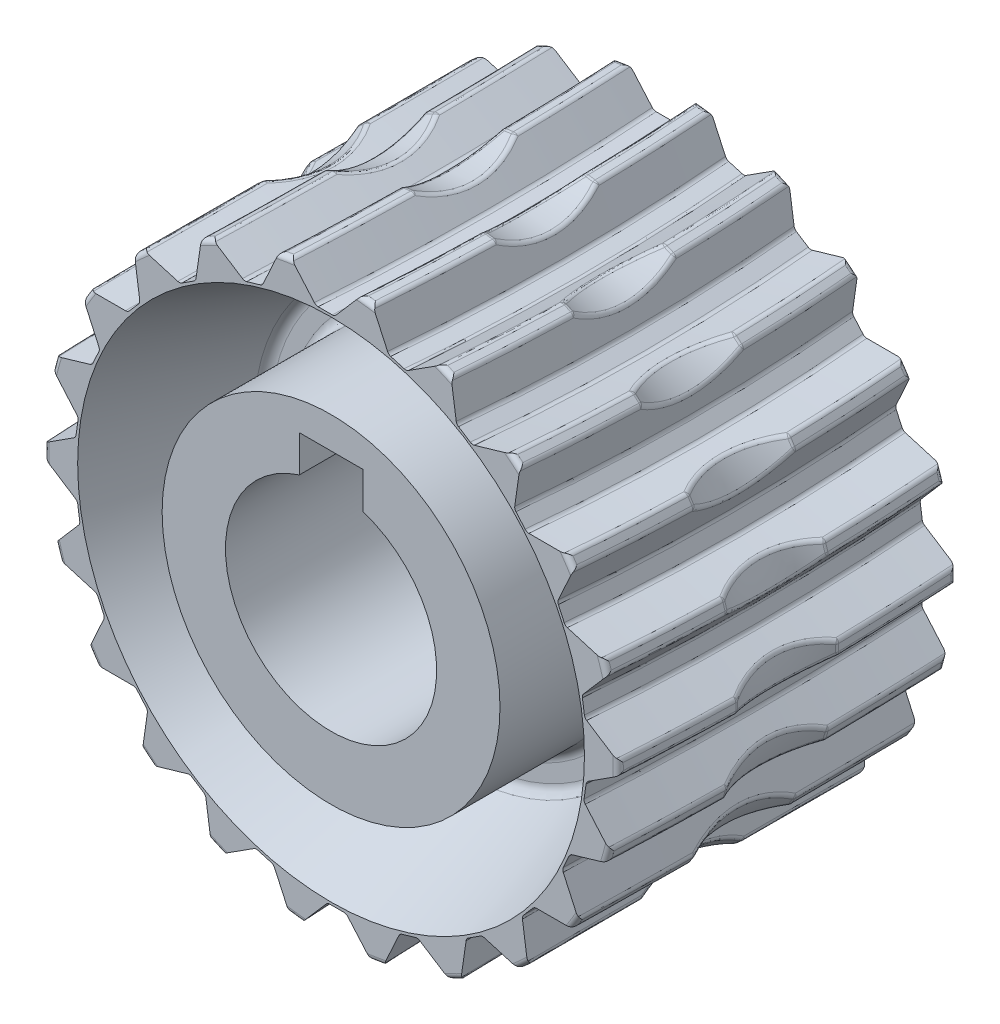
SolidWorks part; units mm, degrees
material "AISI 1020"
ref_plane "Front Plane" through (0, 0, 0) normal (0, 0, 1) x (1, 0, 0)
ref_plane "Top Plane" through (0, 0, 0) normal (0, 1, 0) x (1, 0, 0)
ref_plane "Right Plane" through (0, 0, 0) normal (1, 0, 0) x (0, 0, -1)
sketch "Sketch2" plane through (0, 0, 0) normal (0, 0, 1) x (1, 0, 0)
  circle A0 centre (0, 0) radius 7.9375
  circle A1 centre (0, 0) radius 28.575
  dimension "D1" = 57.15
  dimension "D2" = 15.875
extrude "Boss-Extrude1" add sketch "Sketch2" along normal mid plane 25.4
sketch "Sketch3" plane through (0, 0, 0) normal (1, 0, 0) x (0, 0, -1)
  line L0 (0, 0) -> (15.24, 0) construction
  line L1 (1316.2087, 0) -> (-1316.2087, 0) construction
  line L2 (12.7, 28.575) -> (-12.7, 28.575) construction
  circle A0 centre (0, 28.575) radius 7.9375
  dimension "D1" = 15.875
  dimension "D2" = 15.24
revolve "Cut-Revolve1" cut sketch "Sketch3" angle 360 about L0
sketch "Sketch4" plane through (0, 0, 0) normal (1, 0, 0) x (0, 0, -1)
  line L0 (0, 0) -> (14.4632, 0) construction
  line L1 (56.8636, 0) -> (-56.8636, 0) construction
  line L2 (12.7, 19.05) -> (2.54, 15.24)
  line L3 (12.7, -28.575) -> (12.7, 28.575) construction
  line L4 (2.54, 15.24) -> (2.54, 12.7)
  line L5 (2.54, 12.7) -> (12.7, 12.7)
  line L6 (12.7, 12.7) -> (12.7, 19.05)
  line L7 (0, 0) -> (0, 50.8) construction
  line L8 (-12.7, 12.7) -> (-12.7, 19.05)
  line L9 (-2.54, 12.7) -> (-12.7, 12.7)
  line L10 (-2.54, 15.24) -> (-2.54, 12.7)
  line L11 (-12.7, 19.05) -> (-2.54, 15.24)
  dimension "D2" = 19.05
  dimension "D1" = 14.4632
  dimension "D3" = 12.7
  dimension "D4" = 10.16
  dimension "D5" = 2.54
  dimension "D6" = 50.8
revolve "Cut-Revolve2" cut sketch "Sketch4" angle 360 about L0
chamfer "Chamfer1" distance 2.54 angle 45 2 edges at (28.575, 0, -12.7) (28.575, 0, 12.7)
fillet "Fillet1" radius 0.7874 4 edges at (12.7, 0, 2.54) (12.7, 0, -2.54) (15.24, 0, -2.54) (15.24, 0, 2.54)
sketch "Sketch5" plane through (0, 0, 0) normal (0, 0, 1) x (1, 0, 0)
  line L1 (-2.3876, 0) -> (2.3876, 0)
  line L2 (-2.3876, 0) -> (-2.3876, 10.3251)
  line L3 (-2.3876, 10.3251) -> (2.3876, 10.3251)
  line L4 (2.3876, 0) -> (2.3876, 10.3251)
  circle A1 centre (0, 0) radius 7.9375 construction
  point P4 (0, 0)
  dimension "D1" = 4.7752
  dimension "D2" = 2.3876
extrude "Cut-Extrude1" cut sketch "Sketch5" against normal through all both and the other way through all
ref_plane "Plane1" through (0, 24.13, 0) normal (0, 1, 0) x (1, 0, 0)
sketch "Sketch7" plane through (0, 24.13, 0) normal (0, 1, 0) x (1, 0, 0)
  line L0 (26.035, 12.7) -> (-26.035, 12.7) construction
  arc A0 (-0.635, 15.24) -> (-0.635, -15.24) centre (-183.1975, 0) cw
  dimension "D1" = 0.635
  dimension "D2" = 2.54
ref_plane "profile plane" through (-0.635, 24.13, 15.24) normal (-0.0832, 0, 0.9965) x (0.9965, 0, 0.0832)
sketch "Sketch9" plane through (0, 0, 0) normal (1, 0, 0) x (0, 0, -1)
  line L0 (-12.7, 26.035) -> (-12.7, -26.035) construction
  line L1 (-12.7, 21.59) -> (12.7, 21.59)
  line L2 (-12.7, 21.59) -> (-12.7, 28.575)
  line L3 (-12.7, 28.575) -> (12.7, 28.575)
  line L4 (12.7, 21.59) -> (12.7, 28.575)
  line L5 (56.8636, 0) -> (-56.8636, 0) construction
  line L6 (12.7, -26.035) -> (12.7, 26.035) construction
  line L7 (10.16, 28.575) -> (7.9375, 28.575) construction
  dimension "D1" = 21.59
sketch "Sketch11" plane through (0, 0, 0) normal (0, 1, 0) x (1, 0, 0)
  line L0 (0, 52.4298) -> (0, -31.043)
  line L1 (0, -44.8178) -> (0, 44.8178) construction
revolve "Cut-Revolve3" cut sketch "Sketch9" angle 360 about L0
sketch "Sketch12" plane through (-0.635, 24.13, 15.24) normal (-0.0832, 0, 0.9965) x (0.9965, 0, 0.0832)
  line L0 (-0.6985, -4.9022) -> (0.6985, -4.9022)
  line L1 (0.6985, -4.9022) -> (4.9503, 0)
  line L2 (4.9503, 0) -> (-4.9503, 0)
  line L3 (-4.9503, 0) -> (-0.6985, -4.9022)
  line L4 (-2.3483, -2.9972) -> (2.3507, -2.9972) construction
  line L6 (0, -4.9022) -> (0, 11.1289) construction
  point P8 (-2.3483, -2.9972)
  point P10 (2.3507, -2.9972)
  point P12 (0, 0)
  dimension "D1" = 1.397
  dimension "D2" = 1.905
  dimension "D3" = 2.9972
  dimension "D4" = 4.699
sweep "Cut-Sweep1" cut profiles "Sketch12" path "Sketch7"
fillet "Fillet2" radius 0.381 2 edges at (-0.6985, 19.2278, 0) (0.6985, 19.2278, 0)
pattern_circular "CirPattern1" count 22 over 360 about axis through (0, 0, -52.4298) along (0, 0, 1) of "Cut-Sweep1", "Fillet2" reverse direction yes
fillet "Fillet3" radius 0.381 220 edges at (-14.4395, 16.0509, -12.7) (-18.3766, 11.3326, -12.7) (-20.825, 5.6963, -12.7) (-21.5863, -0.4015, -12.7) (-20.5987, -6.4668, -12.7) (-19.504, -6.8463, -0.7257) (-20.7055, -6.1165, -3.7701) (-20.1013, -4.7789, 0.6177) (-20.7055, -6.1165, 3.7701) (-20.5987, -6.4668, 12.7) (-20.6428, -1.074, -0.7257) (-21.59, -0.0354, -3.7701) (-20.6334, 1.0778, 0.6177) (-21.59, -0.0354, 3.7701) (-21.5863, -0.4015, 12.7) (-20.1092, 4.7852, -0.7257) (-20.7254, 6.0487, -3.7701) (-19.494, 6.8473, 0.6177) (-20.7254, 6.0487, 3.7701) (-20.825, 5.6963, 12.7) (-17.9465, 10.2568, -0.7257) (-18.1818, 11.6427, -3.7701) (-16.7752, 12.062, 0.6177) (-18.1818, 11.6427, 3.7701) (-18.3766, 11.3326, 12.7) (-14.3299, 14.8975, -0.7257) (-14.1651, 16.2935, -3.7701) (-12.6974, 16.2995, 0.6177) (-14.1651, 16.2935, 3.7701) (-14.4395, 16.0509, 12.7) (-9.3325, 19.4688, -12.7) (-9.5523, 18.3312, -0.7257) (-9.001, 19.6242, -3.7701) (-7.591, 19.2166, 0.6177) (-9.001, 19.6242, 3.7701) (-9.3325, 19.4688, 12.7) (-17.9424, -12.0082, 12.7) (-18.1435, -11.7022, 3.7701) (-16.7852, -12.0639, -0.7257) (-17.9407, -10.2485, 0.6177) (-17.9424, -12.0082, -12.7) (-18.1435, -11.7022, -3.7701) (-13.8325, -16.5768, 12.7) (-14.1117, -16.3398, 3.7701) (-12.7065, -16.3041, -0.7257) (-14.3266, -14.8879, 0.6177) (-13.8325, -16.5768, -12.7) (-14.1117, -16.3398, -3.7701) (-8.602, -19.8024, -12.7) (-7.5984, -19.2235, -0.7257) (-8.9366, -19.6536, -3.7701) (-9.5519, -18.3211, 0.6177) (-8.9366, -19.6536, 3.7701) (-8.602, -19.8024, 12.7) (-2.6746, -21.4237, 12.7) (-3.0376, -21.3752, 3.7701) (-1.8747, -20.5856, -0.7257) (-4.0033, -20.27, 0.6177) (-2.6746, -21.4237, -12.7) (-3.0376, -21.3752, -3.7701) (3.4695, -21.3094, -12.7) (4.0009, -20.2799, -0.7257) (3.1076, -21.3652, -3.7701) (1.8696, -20.5768, 0.6177) (3.1076, -21.3652, 3.7701) (3.4695, -21.3094, 12.7) (9.3325, -19.4688, 12.7) (9.001, -19.6242, 3.7701) (9.5523, -18.3312, -0.7257) (7.591, -19.2166, 0.6177) (9.3325, -19.4688, -12.7) (9.001, -19.6242, -3.7701) (14.4395, -16.0509, -12.7) (14.3299, -14.8975, -0.7257) (14.1651, -16.2935, -3.7701) (12.6974, -16.2995, 0.6177) (14.1651, -16.2935, 3.7701) (14.4395, -16.0509, 12.7) (18.3766, -11.3326, 12.7) (18.3766, -11.3326, -12.7) (18.1818, -11.6427, 3.7701) (17.9465, -10.2568, -0.7257) (18.1818, -11.6427, -3.7701) (16.7752, -12.062, 0.6177) (20.825, -5.6963, -12.7) (20.1092, -4.7852, -0.7257) (20.7254, -6.0487, -3.7701) (19.494, -6.8473, 0.6177) (20.7254, -6.0487, 3.7701) (20.825, -5.6963, 12.7) (21.5863, 0.4015, -12.7) (21.5863, 0.4015, 12.7) (21.59, 0.0354, 3.7701) (20.6428, 1.074, -0.7257) (21.59, 0.0354, -3.7701) (20.6334, -1.0778, 0.6177) (20.5987, 6.4668, 12.7) (20.5987, 6.4668, -12.7) (20.7055, 6.1165, 3.7701) (19.504, 6.8463, -0.7257) (20.7055, 6.1165, -3.7701) (20.1013, 4.7789, 0.6177) (17.9424, 12.0082, 12.7) (18.1435, 11.7022, 3.7701) (16.7852, 12.0639, -0.7257) (17.9407, 10.2485, 0.6177) (17.9424, 12.0082, -12.7) (18.1435, 11.7022, -3.7701) (13.8325, 16.5768, 12.7) (14.1117, 16.3398, 3.7701) (12.7065, 16.3041, -0.7257) (14.3266, 14.8879, 0.6177) (13.8325, 16.5768, -12.7) (14.1117, 16.3398, -3.7701) (8.602, 19.8024, 12.7) (8.9366, 19.6536, 3.7701) (7.5984, 19.2235, -0.7257) (9.5519, 18.3211, 0.6177) (8.602, 19.8024, -12.7) (8.9366, 19.6536, -3.7701) (2.6746, 21.4237, 12.7) (3.0376, 21.3752, 3.7701) (1.8747, 20.5856, -0.7257) (4.0033, 20.27, 0.6177) (2.6746, 21.4237, -12.7) (3.0376, 21.3752, -3.7701) (-3.4695, 21.3094, 12.7) (-1.8696, 20.5768, 0.6177) (-3.1076, 21.3652, 3.7701) (-4.0009, 20.2799, -0.7257) (-3.1076, 21.3652, -3.7701) (-3.4695, 21.3094, -12.7)
